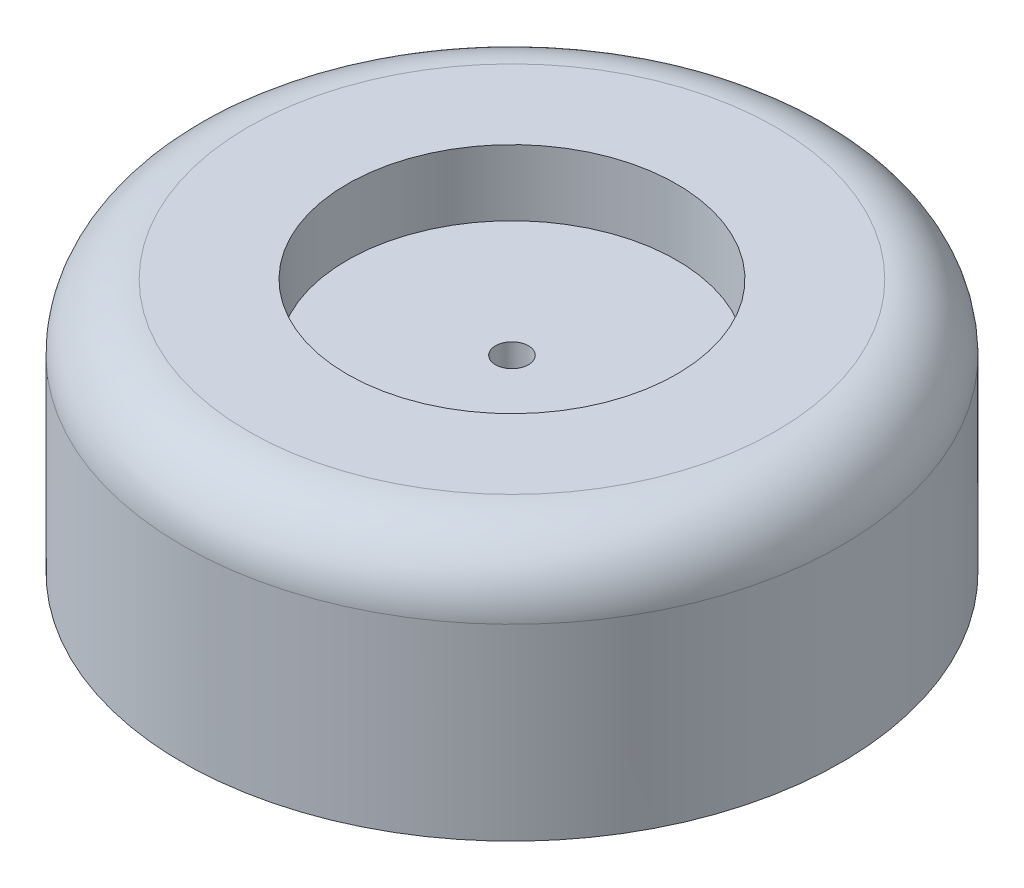
SolidWorks part; units mm, degrees
ref_plane "Front Plane" through (0, 0, 0) normal (0, 0, 1) x (1, 0, 0)
ref_plane "Top Plane" through (0, 0, 0) normal (0, 1, 0) x (1, 0, 0)
ref_plane "Right Plane" through (0, 0, 0) normal (1, 0, 0) x (0, 0, -1)
sketch "Sketch1" plane through (0, 0, 0) normal (0, 1, 0) x (1, 0, 0)
  circle A0 centre (0, 0) radius 47.5
  circle A1 centre (0, 0) radius 50
  dimension "Flange Outer Diameter" = 95
  dimension "Flange Main thickness" = 2.5
extrude "Boss-Extrude1" add sketch "Sketch1" along normal blind 10
sketch "Sketch2" plane through (0, 10, 0) normal (0, 1, 0) x (1, 0, 0)
  circle A0 centre (0, 0) radius 50 construction
  circle A1 centre (0, 0) radius 50
extrude "Boss-Extrude2" add sketch "Sketch2" along normal blind 30
sketch "Sketch3" plane through (0, 10, 0) normal (0, -1, 0) x (1, 0, 0)
  circle A0 centre (0, 0) radius 42.5
  dimension "Bearing track diameter" = 85
sketch "Sketch4" plane through (0, 0, 0) normal (0, 0, 1) x (1, 0, 0)
  line L0 (0, 0) -> (0, 10) construction
  line L1 (-42.5, 10) -> (42.5, 10) construction
  line L2 (0, 10) -> (42.5, 10) construction
  circle A0 centre (42.5, 10) radius 2.5
  dimension "Bearing Ball OD" = 5
  dimension "Bearing track radius" = 42.5
sweep "Cut-Sweep1" cut profiles "Sketch4" path "Sketch3"
sketch "Sketch5" plane through (0, 10, 0) normal (0, -1, 0) x (1, 0, 0)
  circle A0 centre (0, 0) radius 47.5 construction
  circle A1 centre (0, 0) radius 47.5
extrude "Cut-Extrude1" cut sketch "Sketch5" against normal blind 1 contours A1
sketch "Sketch6" plane through (0, 0, 0) normal (0, -1, 0) x (1, 0, 0)
  circle A0 centre (0, 0) radius 50 construction
  circle A1 centre (0, 0) radius 50
extrude "Cut-Extrude2" cut sketch "Sketch6" against normal blind 1.5
sketch "Sketch7" plane through (0, 40, 0) normal (0, 1, 0) x (1, 0, 0)
  circle A0 centre (0, 0) radius 2.5
  dimension "Center Bolt OD" = 5
extrude "Cut-Extrude3" cut sketch "Sketch7" against normal through all and the other way through all
sketch "Sketch8" plane through (0, 11, 0) normal (0, -1, 0) x (1, 0, 0)
  circle A0 centre (0, 0) radius 35
  dimension "Pulley hole" = 70
extrude "Cut-Extrude4" cut sketch "Sketch8" against normal blind 5
fillet "Fillet1" radius 10 1 edges at (0, 40, 50)
sketch "Sketch9" plane through (0, 40, 0) normal (0, 1, 0) x (1, 0, 0)
  circle A0 centre (0, 0) radius 25
  dimension "Flange attachment hole" = 50
extrude "Cut-Extrude5" cut sketch "Sketch9" against normal blind 10
